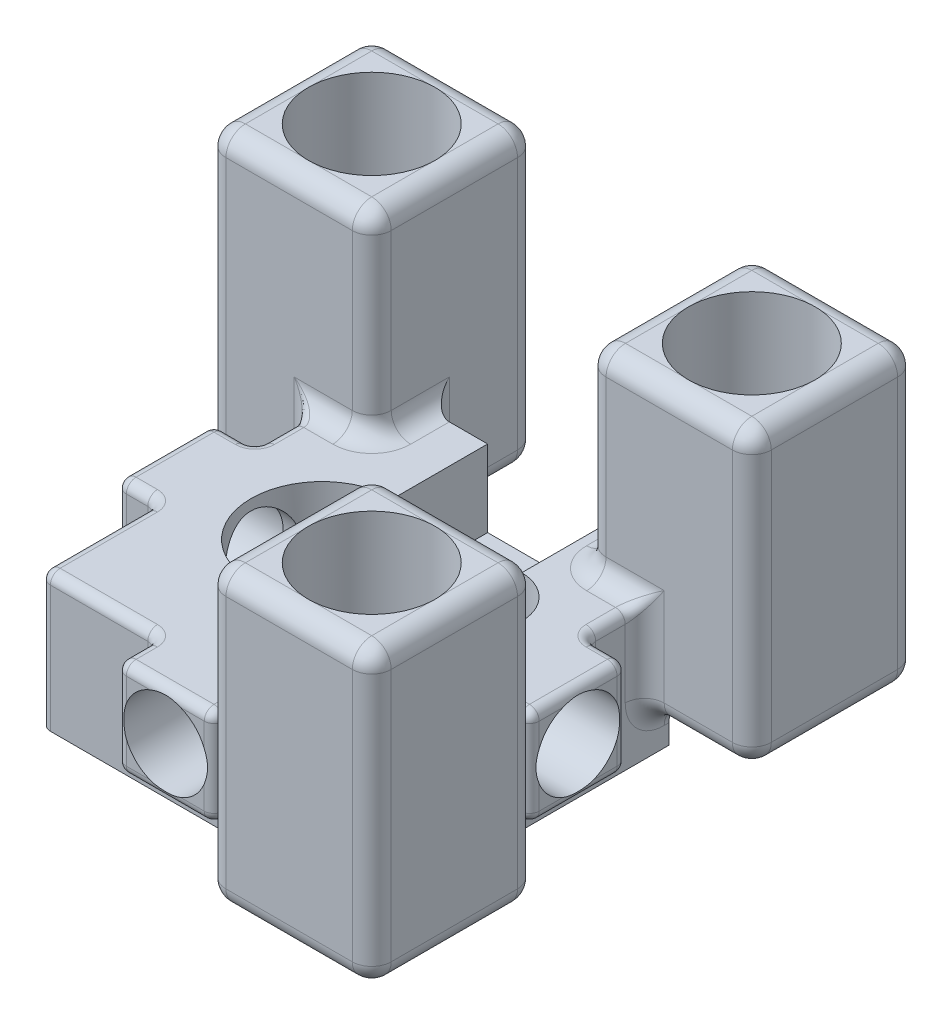
SolidWorks part; units mm, degrees
ref_plane "Front Plane" through (0, 0, 0) normal (0, 0, 1) x (1, 0, 0)
ref_plane "Top Plane" through (0, 0, 0) normal (0, 1, 0) x (1, 0, 0)
ref_plane "Right Plane" through (0, 0, 0) normal (1, 0, 0) x (0, 0, -1)
sketch "Sketch1" plane through (0, 0, 0) normal (0, 1, 0) x (1, 0, 0)
  line L0 (0, -2.5) -> (6.6, -2.5)
  line L1 (0, 2.5) -> (6.6, 2.5)
  line L2 (7.6, -1.5) -> (7.6, 1.5)
  line L3 (0, -3.65) -> (6.6, -3.65)
  line L4 (0, 3.65) -> (6.6, 3.65)
  line L5 (8.75, -1.5) -> (8.75, 1.5)
  line L7 (-3.65, -3.65) -> (8.75, -3.65) construction
  line L8 (-3.65, -3.65) -> (-3.65, 3.65) construction
  line L9 (-3.65, 3.65) -> (8.75, 3.65) construction
  line L10 (8.75, -3.65) -> (8.75, 3.65) construction
  line L11 (-3.65, -3.65) -> (8.75, 3.65) construction
  line L12 (-3.65, 3.65) -> (8.75, -3.65) construction
  line L13 (-5.95, -8.5) -> (11.05, -8.5)
  line L14 (-5.95, -8.5) -> (-5.95, 8.5)
  line L15 (-5.95, 8.5) -> (11.05, 8.5)
  line L16 (11.05, -8.5) -> (11.05, 8.5)
  line L17 (-5.95, -8.5) -> (11.05, 8.5) construction
  line L18 (-5.95, 8.5) -> (11.05, -8.5) construction
  arc A0 (0, -2.5) -> (0, 2.5) centre (0, 0) cw
  arc A1 (7.6, -1.5) -> (6.6, -2.5) centre (6.6, -1.5) cw
  arc A2 (6.6, 2.5) -> (7.6, 1.5) centre (6.6, 1.5) cw
  arc A3 (8.75, -1.5) -> (6.6, -3.65) centre (6.6, -1.5) cw
  arc A4 (0, -3.65) -> (0, 3.65) centre (0, 0) cw
  arc A5 (6.6, 3.65) -> (8.75, 1.5) centre (6.6, 1.5) cw
  point P8 (2.55, 0)
  point P24 (2.55, 0)
  dimension "D1" = 2.5
  dimension "D3" = 1
  dimension "D2" = 6.6
  dimension "D5" = 17
  dimension "D4" = 1.15
extrude "Boss-Extrude1" add sketch "Sketch1" against normal blind 7 contours L15 L16 L13 L14
extrude "Cut-Extrude1" cut sketch "Sketch1<3>" against normal blind 3.25 contours L3 A3 L5 A5 L4 A4
sketch "Sketch1<3>" plane through (0, 0, 0) normal (0, 1, 0) x (1, 0, 0) same geometry as "Sketch1"
extrude "Cut-Extrude2" cut sketch "Sketch1<4>" against normal blind 3.94 contours A0 L1 A2 L2 A1 L0
sketch "Sketch1<4>" plane through (0, 0, 0) normal (0, 1, 0) x (1, 0, 0) same geometry as "Sketch1"
sketch "Sketch2" plane through (0, 0, 0) normal (0, 1, 0) x (1, 0, 0)
  line L0 (-5.95, 8.5) -> (11.05, -8.5) construction
  line L1 (-11.45, 14) -> (-2.9647, 14)
  line L2 (-11.45, 14) -> (-11.45, 5.5147)
  line L3 (-11.45, 5.5147) -> (-2.9647, 5.5147)
  line L4 (-2.9647, 14) -> (-2.9647, 5.5147)
  line L5 (-11.45, 14) -> (-2.9647, 5.5147) construction
  line L6 (-11.45, 5.5147) -> (-2.9647, 14) construction
  line L7 (-5.95, -8.5) -> (-5.95, 8.5) construction
  point P0 (-7.2074, 9.7574)
  dimension "D1" = 6
  dimension "D2" = 5.5
extrude "Boss-Extrude2" add sketch "Sketch2" along normal blind 10 and the other way blind 5
sketch "Sketch3" plane through (0, 10, 0) normal (0, 1, 0) x (1, 0, 0)
  line L0 (-2.9647, 14) -> (-11.45, 5.5147) construction
  circle A0 centre (-7.2074, 9.7574) radius 3.25
  dimension "D1" = 6.5
extrude "Cut-Extrude3" cut sketch "Sketch3" against normal through all both and the other way through all
sketch "Sketch4" plane through (0, 0, 0) normal (0, 0, 1) x (1, 0, 0)
  line L0 (2.55, 0) -> (2.55, 7.7901) construction
fillet "Fillet1" radius 1 18 edges at (-3.5876, -5, -8.5) (-5.95, -5, -6.1376) (-2.9647, 10, -9.7574) (-2.9647, -5, -11.25) (-2.9647, -2.5, -8.5) (-2.9647, 0, -7.0074) (-7.2074, -5, -14) (-2.9647, 2.5, -14) (-7.2074, 10, -14) (-11.45, -5, -9.7574) (-11.45, 2.5, -14) (-11.45, 10, -9.7574) (-5.95, -2.5, -5.5147) (-8.7, -5, -5.5147) (-11.45, 2.5, -5.5147) (-7.2074, 10, -5.5147) (-2.9647, 5, -5.5147) (-4.4574, 0, -5.5147)
pattern_circular "CirPattern3" count 3 over 180 about axis through (2.55, 0, 0) along (0, 1, 0) of "Boss-Extrude2", "Cut-Extrude3", "Fillet1" reverse direction yes
sketch "Sketch5" plane through (-5.95, 0, 0) normal (-1, 0, 0) x (0, 0, 1)
  line L1 (-2.5, -5) -> (2.5, -5)
  line L2 (-2.5, -5) -> (-2.5, 0)
  line L3 (-2.5, 0) -> (2.5, 0)
  line L4 (2.5, -5) -> (2.5, 0)
  line L5 (-2.5, -5) -> (2.5, 0) construction
  line L6 (-2.5, 0) -> (2.5, -5) construction
  circle A0 centre (0, -2.5) radius 2.15
  circle A1 centre (0, -2.5) radius 1.95
  point P0 (0, 0)
  point P1 (0, -2.5)
  line M10 (8.5, 0) -> (-4.5147, 0)
  dimension "D2" = 4.3
  dimension "D3" = 3.9
  dimension "D1" = 5
extrude "Boss-Extrude3" add sketch "Sketch5" along normal blind 2.1 contours L1 L4 L2 A0 M10 region at (-5.95, -2.5, -2.4293)
extrude "Cut-Extrude4" cut sketch "Sketch5<3>" against normal blind 2 contours A0 A1 region at (-5.95, -2.5, -2.0892)
sketch "Sketch5<3>" plane through (-5.95, 0, 0) normal (-1, 0, 0) x (0, 0, 1) same geometry as "Sketch5"
extrude "Cut-Extrude5" cut sketch "Sketch5<4>" against normal blind 6 contours A1 region at (-5.95, -2.5, 0)
sketch "Sketch5<4>" plane through (-5.95, 0, 0) normal (-1, 0, 0) x (0, 0, 1) same geometry as "Sketch5"
fillet "Fillet3" radius 0.5 14 edges at (-6.2429, 0.2929, -5.2218) (-5.95, 0, -3.5074) (-5.95, 0, 5.5) (-8.05, -5, 0) (-5.95, -5, 0) (-7, 0, -2.5) (-8.05, -2.5, -2.5) (-7, -5, -2.5) (-5.95, -2.5, -2.5) (-7, -5, 2.5) (-8.05, -2.5, 2.5) (-7, 0, 2.5) (-5.95, -2.5, 2.5) (-8.05, 0, 0)
pattern_circular "CirPattern5" count 4 every 90 about axis through (2.55, 0, 0) along (0, 1, 0) skipping 3 of "Boss-Extrude3", "Cut-Extrude4", "Cut-Extrude5", "Fillet3"
sketch "Sketch6" plane through (0, -7, 0) normal (0, 1, 0) x (1, 0, 0)
  line L0 (0, 2.5) -> (5, 2.5)
  line L1 (5, 2.5) -> (5, -2.5)
  line L2 (5, -2.5) -> (0, -2.5)
  line L3 (4.5, 2) -> (4.5, -2)
  line L4 (4.5, -2) -> (0, -2)
  line L5 (0, 2) -> (4.5, 2)
  arc A0 (0, 2.5) -> (0, -2.5) centre (0, 0) ccw
  arc A1 (0, 2.5) -> (-2.1263, 1.3149) centre (0, 0) ccw construction
  arc A2 (0, 2) -> (0, -2) centre (0, 0) ccw
  dimension "D1" = 5
  dimension "D2" = 0.5
extrude "Boss-Extrude4" add sketch "Sketch6" against normal blind 6 contours L3 L4 A2 L5 | L2 A0 L0 L1
extrude "Cut-Extrude6" cut sketch "Sketch6<3>" along normal through all contours L3 L4 A2 L5
sketch "Sketch6<3>" plane through (0, -7, 0) normal (0, 1, 0) x (1, 0, 0) same geometry as "Sketch6"
sketch "Sketch7" plane through (0, -7, 0) normal (0, -1, 0) x (1, 0, 0)
  line L0 (9.0647, 14) -> (15.55, 14) construction
  line L1 (-11.45, -14) -> (16.55, -14)
  line L2 (-11.45, -14) -> (-11.45, 14)
  line L3 (-11.45, 14) -> (16.55, 14)
  line L4 (16.55, -14) -> (16.55, 14)
  line L5 (16.55, -6.5147) -> (16.55, -13) construction
  line L8 (5, 2.5) -> (5, -2.5)
  line L9 (5, -2.5) -> (0, -2.5)
  line L10 (5, 2.5) -> (0, 2.5)
  line L11 (5, 2.5) -> (0, 2.5) construction
  line L12 (5, 2.5) -> (0, 2.5) construction
  circle A0 centre (-7.2074, -9.7574) radius 3.25
  circle A1 centre (12.3074, -9.7574) radius 3.25
  circle A2 centre (12.3074, 9.7574) radius 3.25
  arc A3 (-3.9647, -9.5388) -> (-3.9676, -9.5) centre (-7.2074, -9.7574) ccw construction
  arc A4 (0, 2.5) -> (0, -2.5) centre (0, 0) ccw
sketch "Sketch8" plane through (0, 0, -3.65) normal (0, 0, 1) x (1, 0, 0)
  line L1 (0, 0) -> (6.6, 0)
  line L2 (0, 0) -> (0, -3.94)
  line L3 (0, -3.94) -> (6.6, -3.94)
  line L4 (6.6, 0) -> (6.6, -3.94)
  point P6 (0, 0)
extrude "Cut-Extrude7" cut sketch "Sketch8" against normal through all
